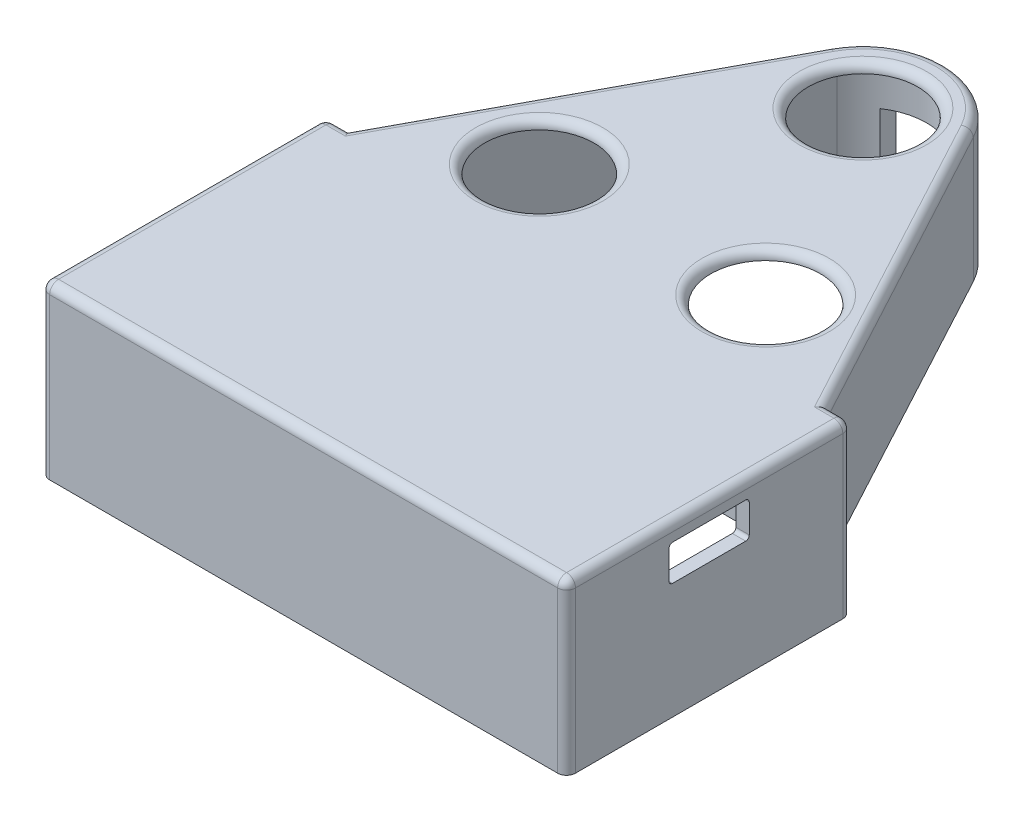
SolidWorks part; units mm, degrees
note: The reader was unsure of these and kept them because the rebuilt part matched: shared geometry of "Sketch1<7>".
ref_plane "Front Plane" through (0, 0, 0) normal (0, 0, 1) x (1, 0, 0)
ref_plane "Top Plane" through (0, 0, 0) normal (0, 1, 0) x (1, 0, 0)
ref_plane "Right Plane" through (0, 0, 0) normal (1, 0, 0) x (0, 0, -1)
sketch "Sketch1" plane through (0, 0, 0) normal (0, 1, 0) x (1, 0, 0)
  line L0 (-12.7, 0) -> (12.7, 0) construction
  line L1 (0, 0) -> (0, 23.62) construction
  line L2 (-12.7, -6.14) -> (12.7, -6.14) construction
  line L3 (0, 23.62) -> (0, 29.76) construction
  line L4 (-5.4079, 26.5277) -> (-18.1079, 2.9077) construction
  line L5 (5.4079, 26.5277) -> (18.1079, 2.9077) construction
  line L6 (-10.45, 0) -> (10.45, 0) construction
  line L7 (-18.84, 0) -> (18.84, 0) construction
  line L8 (0, -10.45) -> (0, 10.45) construction
  line L9 (-6.2886, 27.0013) -> (-18.9886, 3.3813)
  line L10 (-12.7, -7.14) -> (12.7, -7.14)
  line L11 (6.2886, 27.0013) -> (18.9886, 3.3813)
  line L12 (-26.9165, -7.14) -> (-8.0501, 27.9484)
  line L13 (-12.7, -7.14) -> (12.7, -7.14)
  line L14 (8.0501, 27.9484) -> (26.9165, -7.14)
  line L15 (-29.5, -7.14) -> (29.5, -7.14)
  line L16 (29.5, -7.14) -> (29.5, -39.14)
  line L17 (29.5, -39.14) -> (-29.5, -39.14)
  line L18 (-29.5, -39.14) -> (-29.5, -7.14)
  line L19 (-18.9886, 3.3813) -> (-24.6457, -7.14)
  line L20 (-28, -8.64) -> (28, -8.64)
  line L21 (-28, -8.64) -> (-28, -37.64)
  line L22 (-28, -37.64) -> (28, -37.64)
  line L23 (28, -8.64) -> (28, -37.64)
  line L24 (-28, -8.64) -> (28, -37.64) construction
  line L25 (-28, -37.64) -> (28, -8.64) construction
  line L26 (18.9886, 3.3813) -> (24.6457, -7.14)
  line L27 (-26.9165, -7.14) -> (-24.6457, -7.14)
  line L28 (24.6457, -7.14) -> (26.9165, -7.14)
  circle A0 centre (-12.7, 0) radius 6.14
  circle A1 centre (0, 23.62) radius 6.14
  circle A2 centre (12.7, 0) radius 6.14
  circle A3 centre (0, 23.62) radius 7.14 construction
  circle A4 centre (12.7, 0) radius 7.14 construction
  circle A5 centre (-12.7, 0) radius 7.14 construction
  circle A6 centre (0, 23.62) radius 9.14 construction
  arc A8 (8.0501, 27.9484) -> (-8.0501, 27.9484) centre (0, 23.62) ccw
  arc A9 (-6.2886, 27.0013) -> (6.2975, 26.9847) centre (0, 23.62) cw
  point P29 (-21.8171, -1.8794)
  point P38 (0, -23.14)
  point P41 (0, -7.14)
  dimension "D4" = 1
  dimension "D6" = 2
  dimension "D1" = 23.62
  dimension "D2" = 25.4
  dimension "D3" = 35.9
  dimension "D5" = 1
  dimension "D7" = 2
  dimension "D8" = 59
  dimension "D9" = 32
  dimension "D10" = 1.5
  dimension "D11" = 1.5
  dimension "D12" = 1.5
  dimension "D13" = 1.5
extrude "Boss-Extrude1" add sketch "Sketch1" along normal blind 1 contours L18 L17 L16 L15 L10 L20 L23 L22 L21 | L23 L20 L21 L22 | A6 L12 L15 L19 L9 | A6 L9 A5 L10 A4 L11 | A5 | A5 L19 L15 | A3 | A6 L11 L26 L15 L14 | A4 | A4 L15 L26 | L11 A6 L9 A3 | L9 A6 L11 A3
extrude "Boss-Extrude2" add sketch "Sketch1<7>" against normal blind 18 contours L18 L17 L16 L15 L10 L20 L23 L22 L21 | L23 L20 L21 L22
sketch "Sketch1<7>" plane through (0, 0, 0) normal (0, 1, 0) x (1, 0, 0) same geometry as "Sketch1"
sketch "Sketch16" plane through (0, 0, 0) normal (0, -1, 0) x (1, 0, 0)
  line L0 (-24.6457, 7.14) -> (-6.2886, -27.0013)
  line L1 (-24.6457, 7.14) -> (-26.9165, 7.14)
  line L2 (-26.9165, 7.14) -> (-8.0501, -27.9484)
  line L3 (26.9165, 7.14) -> (8.0501, -27.9484)
  line L4 (26.9165, 7.14) -> (24.6457, 7.14)
  line L5 (24.6457, 7.14) -> (6.2886, -27.0013)
  arc A0 (-8.0501, -27.9484) -> (8.0501, -27.9484) centre (0, -23.62) ccw
  arc A1 (-6.2886, -27.0013) -> (6.2886, -27.0013) centre (0, -23.62) ccw
extrude "Boss-Extrude4" add sketch "Sketch16" along normal blind 14
sketch "Sketch29" plane through (0, -14, 0) normal (0, -1, 0) x (1, 0, 0)
  line L0 (-4, -29.5344) -> (4, -29.5344)
  line L1 (-6.2886, -27.0013) -> (6.2886, -27.0013) construction
  line L4 (-4, -29.5344) -> (-4, -34.5344)
  line L5 (-4, -34.5344) -> (4, -34.5344)
  line L6 (4, -29.5344) -> (4, -34.5344)
  arc A3 (-6.2886, -27.0013) -> (6.2886, -27.0013) centre (0, -23.62) ccw construction
  dimension "D2" = 8
  dimension "D3" = 5
fillet "Fillet1" radius 1 4 edges at (-29.5, -8.5, 39.14) (-29.5, -8.5, 7.14) (29.5, -8.5, 39.14) (29.5, -8.5, 7.14)
sketch "Sketch19" plane through (29.5, 0, 0) normal (1, 0, 0) x (0, 0, -1)
  line L0 (-23.14, 1) -> (-23.14, -18) construction
  line L1 (-8.14, 1) -> (-38.14, 1) construction
  line L2 (-8.14, -18) -> (-38.14, -18) construction
  line L4 (-27.24, -1) -> (-19.04, -1)
  line L5 (-27.64, -1.4) -> (-27.64, -4.6)
  line L6 (-27.24, -5) -> (-19.04, -5)
  line L7 (-18.64, -1.4) -> (-18.64, -4.6)
  line L8 (-27.64, -1) -> (-18.64, -5) construction
  line L9 (-27.64, -5) -> (-18.64, -1) construction
  arc A0 (-19.04, -5) -> (-18.64, -4.6) centre (-19.04, -4.6) ccw
  arc A1 (-19.04, -1) -> (-18.64, -1.4) centre (-19.04, -1.4) cw
  arc A2 (-27.64, -4.6) -> (-27.24, -5) centre (-27.24, -4.6) ccw
  arc A3 (-27.24, -1) -> (-27.64, -1.4) centre (-27.24, -1.4) ccw
  point P6 (-23.14, -3)
  dimension "D4" = 0.4
  dimension "D1" = 2
  dimension "D2" = 4
  dimension "D3" = 9
extrude "Cut-Extrude2" cut sketch "Sketch19" against normal blind 14
sketch "Sketch21" plane through (0, 0, 8.64) normal (0, 0, 1) x (1, 0, 0)
  line L0 (-28, 0) -> (28, 0) construction
  line L1 (-8, 0) -> (8, 0)
  line L2 (-8, 0) -> (-8, -14)
  line L3 (-8, -14) -> (8, -14)
  line L4 (8, 0) -> (8, -14)
  line L5 (-8, -5.9113) -> (-28, -5.9113)
  line L7 (-28, -18) -> (-28, 0) construction
  line L8 (8, -5.9113) -> (28, -5.9113)
  line L9 (28, -18) -> (28, 0) construction
  line M7 (28, 0) -> (-28, 0)
  dimension "D1" = 16
  dimension "D2" = 14
extrude "Cut-Extrude3" cut sketch "Sketch21" against normal blind 14 contours L4 L2 L3 M7
fillet "Fillet2" radius 1 15 edges at (12.7, 1, 6.14) (0, 1, -17.48) (-12.7, 1, 6.14) (-29.2071, 1, 7.4329) (-27.7082, 1, 7.14) (-17.4833, 1, -10.4042) (0, 1, -32.76) (17.4833, 1, -10.4042) (27.7082, 1, 7.14) (29.2071, 1, 7.4329) (29.5, 1, 23.14) (29.2071, 1, 38.8471) (0, 1, 39.14) (-29.2071, 1, 38.8471) (-29.5, 1, 23.14)
ref_plane "Plane1" through (0, -18, 0) normal (0, -1, 0) x (-1, 0, 0)
sketch "Sketch24" plane through (0, -18, 0) normal (0, -1, 0) x (-1, 0, 0)
  line L0 (-28, -8.64) -> (-28, -7.14)
  line L1 (28.5, -7.14) -> (-28.5, -7.14) construction
  line L2 (28, -8.64) -> (28, -7.14)
  line L3 (28, -7.14) -> (-28, -7.14)
  line L4 (28, -8.64) -> (-28, -8.64)
extrude "Cut-Extrude5" cut sketch "Sketch24" against normal blind 4
sketch "Sketch26" plane through (0, 0, 7.14) normal (0, 0, -1) x (-1, 0, 0)
  line L6 (28, -18) -> (26, -18)
  line L7 (28, -18) -> (28, -16.15)
  line L8 (28, -16.15) -> (26, -16.15)
  line L9 (26, -18) -> (26, -16.15)
  line L11 (-28, -18) -> (-26, -18)
  line L12 (-28, -18) -> (-28, -16.15)
  line L13 (-28, -16.15) -> (-26, -16.15)
  line L14 (-26, -18) -> (-26, -16.15)
  dimension "D1" = 1.85
  dimension "D2" = 2
  dimension "D3" = 1.85
  dimension "D4" = 2
extrude "Boss-Extrude5" add sketch "Sketch26" against normal through all
sketch "Sketch27" plane through (26, 0, 0) normal (-1, 0, 0) x (0, 0, 1)
  line L0 (37.64, -16.15) -> (7.14, -16.15) construction
  line L1 (37.64, -18) -> (35.64, -18)
  line L2 (37.64, -18) -> (37.64, -16.15)
  line L3 (37.64, -16.15) -> (35.64, -16.15)
  line L4 (35.64, -18) -> (35.64, -16.15)
  dimension "D1" = 2
extrude "Boss-Extrude6" add sketch "Sketch27" along normal through all
extrude "Cut-Extrude7" cut sketch "Sketch29" against normal blind 10
chamfer "Chamfer1" distance 0.5 angle 45 2 edges at (-4, -9, -31.8382) (4, -9, -31.8382)
chamfer "Chamfer2" distance 0.25 angle 45 4 edges at (27, -16.15, 7.14) (28, -15.075, 7.14) (-27, -16.15, 7.14) (-28, -15.075, 7.14)
